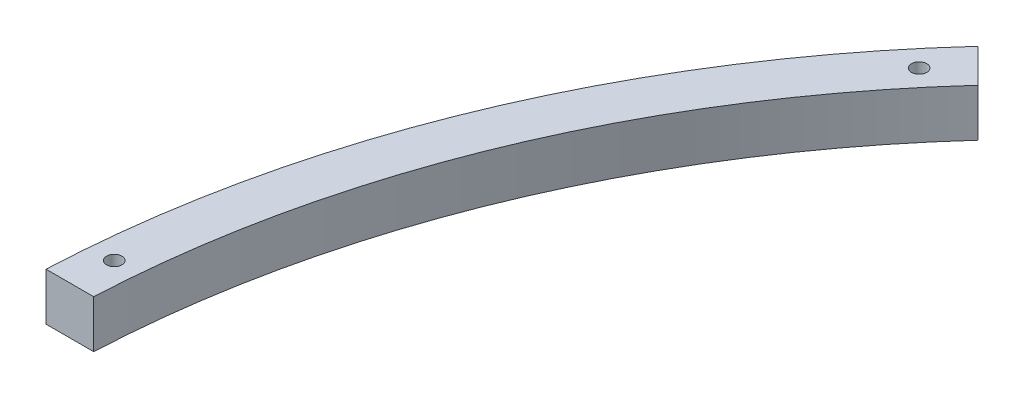
SolidWorks part; units mm, degrees
ref_plane "Front Plane" through (0, 0, 0) normal (0, 0, 1) x (1, 0, 0)
ref_plane "Top Plane" through (0, 0, 0) normal (0, 1, 0) x (1, 0, 0)
ref_plane "Right Plane" through (0, 0, 0) normal (1, 0, 0) x (0, 0, -1)
sketch "Sketch1" plane through (0, 0, 0) normal (0, 1, 0) x (1, 0, 0)
  line L1 (0, 220) -> (0, -220) construction
  line L6 (-220, 0) -> (220, 0) construction
  line L7 (-10, 219.7726) -> (-10, -219.7726) construction
  line L12 (-10, 219.7726) -> (-10, 209.7618)
  line L13 (-219.7726, 10) -> (219.7726, 10) construction
  line L14 (-219.7726, 10) -> (-209.7618, 10)
  line L15 (-155.5635, 155.5635) -> (155.5635, -155.5635) construction
  line L16 (-162.4738, 148.3316) -> (148.3316, -162.4738)
  arc A3 (-10, 219.7726) -> (-219.7726, 10) centre (0, 0) ccw
  arc A4 (-10, 209.7618) -> (-209.7618, 10) centre (0, 0) ccw
  arc A5 (-210, 0) -> (-209.7618, 10) centre (0, 0) ccw construction
  arc A6 (-220, 0) -> (-219.7726, 10) centre (0, 0) ccw construction
  circle A7 centre (0, 0) radius 215 construction
  dimension "D1" = 210
  dimension "D2" = 220
  dimension "D4" = 10
  dimension "D5" = 5
  dimension "D3" = 10
  dimension "D6" = 20
sketch "Sketch14" [suppressed] plane through (0, 0, 0) normal (0, 1, 0) x (1, 0, 0)
  line L0 (-200, 10) -> (200, 10) construction
  line L1 (-10, 200) -> (-10, -200) construction
  line L2 (-200, 10) -> (-189.7367, 10)
  line L3 (-10, 200) -> (-10, 189.7367)
  circle A0 centre (0, 0) radius 200 construction
  circle A1 centre (0, 0) radius 190 construction
  arc A2 (-10, 199.7498) -> (-199.7498, 10) centre (0, 0) ccw
  arc A3 (-10, 189.7367) -> (-189.7367, 10) centre (0, 0) ccw
sketch "roll" plane through (0, 0, 0) normal (0, 1, 0) x (1, 0, 0)
  line L0 (0, -195) -> (0, 195) construction
  dimension "D1" = 390
ref_axis "Axis1" through (0, -148.0362, 0) along (0, 1, 0)
extrude "base" add sketch "Sketch1" along normal mid plane 10 contours A4 L15 A3 L14 region at (-194.7302, 0, -80.6599)
sketch "Sketch25" plane through (0, 5, 0) normal (0, 1, 0) x (1, 0, 0)
  line L0 (-220, 0) -> (220, 0) construction
  line L1 (0, 220) -> (0, -220) construction
  line L2 (-220, 0) -> (220, 0)
  line L3 (0, 220) -> (0, -220)
  line L4 (0, 0) -> (-214.1819, 18.7385) construction
  line L5 (0, 0) -> (-170.571, 130.8837) construction
  line L6 (-155.5635, 155.5635) -> (155.5635, -155.5635) construction
  line L7 (-155.5635, 155.5635) -> (155.5635, -155.5635)
  line L8 (0, 0) -> (-164.6996, 138.1993) construction
  line L9 (0, 0) -> (-213.1606, 28.0631) construction
  circle A0 centre (0, 0) radius 215 construction
  circle A1 centre (0, 0) radius 215 construction
  dimension "D1" = 5
  dimension "D2" = 7.5
  dimension "D3" = 5
  dimension "D4" = 7.5
ref_plane "Plane1" through (0, 0, 0) normal (0.7071, 0, -0.7071) x (0.7071, 0, 0.7071)
hole_wizard "Ø3.2 (3.2) Diameter Hole1" positions "Sketch28" profile "Sketch29" hole size "Ø3.2" standard "ISO" end condition through all
sketch "Sketch28" plane through (0, 5, 0) normal (0, 1, 0) x (1, 0, 0)
  point P14 (-164.6996, 138.1993)
  point P17 (-214.1819, 18.7385)
  point P21 (0, 0)
  point P22 (0, 0)
sketch "Sketch29" plane through (-164.6996, 5, -138.1993) normal (1, 0, 0) x (0, 0, 1)
  line L0 (0, 0) -> (0, 10)
  line L1 (0, 10) -> (1.6, 10)
  line L2 (1.6, 10) -> (1.6, 0)
  line L5 (1.6, 0) -> (0, 0)
  line L11 (0, -6.35) -> (0, 107.95) construction
  dimension "Thru Hole Dia." = 3.2
  dimension "Thru Hole Depth" = 10
